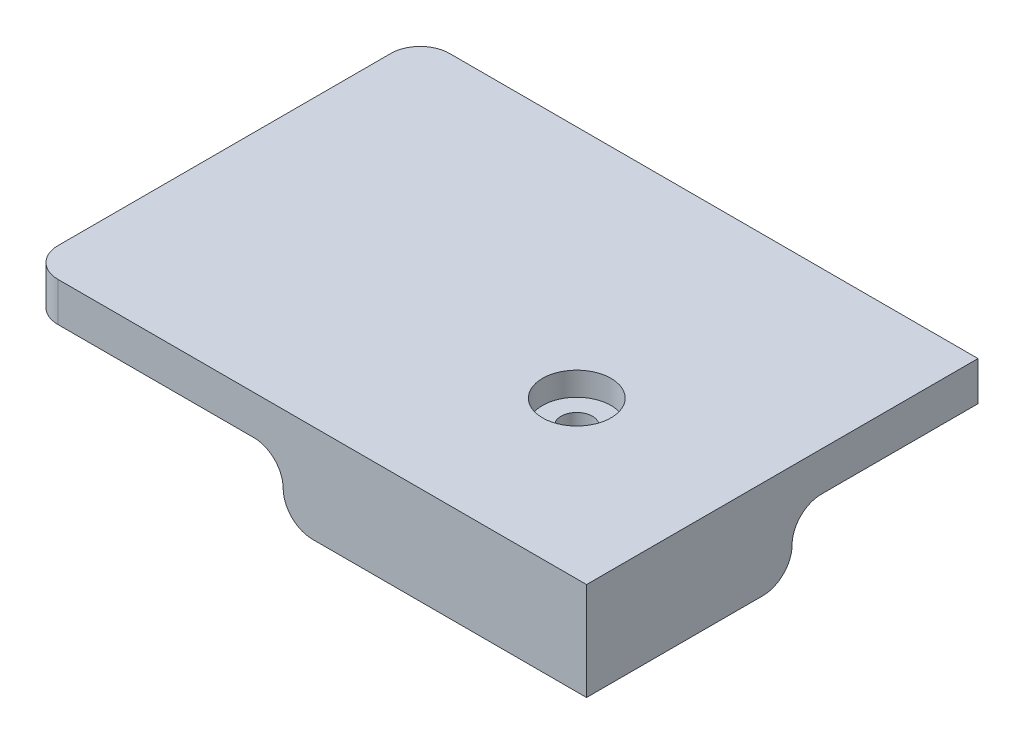
SolidWorks part; units mm, degrees
ref_plane "Front Plane" through (0, 0, 0) normal (0, 0, 1) x (1, 0, 0)
ref_plane "Top Plane" through (0, 0, 0) normal (0, 1, 0) x (1, 0, 0)
ref_plane "Right Plane" through (0, 0, 0) normal (1, 0, 0) x (0, 0, -1)
sketch "Sketch1" plane through (0, 0, 0) normal (0, 1, 0) x (1, 0, 0)
  line L5 (-28.5, 20) -> (28.5, 20)
  line L6 (-28.5, 20) -> (-28.5, -20)
  line L7 (-28.5, -20) -> (28.5, -20)
  line L8 (28.5, 20) -> (28.5, -20)
  line L9 (-28.5, 20) -> (28.5, -20) construction
  line L10 (-28.5, -20) -> (28.5, 20) construction
  point P0 (0, 0)
  dimension "D1" = 57
  dimension "D2" = 40
extrude "Boss-Extrude1" add sketch "Sketch1" against normal blind 4
sketch "Sketch2" plane through (0, -4, 0) normal (0, -1, 0) x (1, 0, 0)
  line L1 (28.5, 20) -> (-2.5, 20)
  line L2 (28.5, 20) -> (28.5, -1)
  line L3 (28.5, -1) -> (-2.5, -1)
  line L4 (-2.5, 20) -> (-2.5, -1)
  point P7 (0, 0)
  dimension "D1" = 21
  dimension "D2" = 31
extrude "Boss-Extrude2" add sketch "Sketch2" along normal blind 6
sketch "Sketch4" plane through (0, 0, 0) normal (0, 1, 0) x (1, 0, 0)
  line L0 (28.5, -20) -> (28.5, 20) construction
  line L1 (-28.5, -20) -> (28.5, -20) construction
  point P0 (11.5, -4)
  dimension "D1" = 17
  dimension "D2" = 16
hole_wizard "CBORE for M3 Pan Head Screw1" positions "Sketch5" profile "Sketch6" counterbore size "M3" standard "JIS" end condition up to next
sketch "Sketch5" plane through (0, 0, 0) normal (0, 1, 0) x (1, 0, 0)
  point P0 (11.5, -4)
sketch "Sketch6" plane through (11.5, 0, 4) normal (1, 0, 0) x (0, 0, 1)
  line L0 (0, 0) -> (0, 10)
  line L1 (0, 10) -> (1.6, 10)
  line L3 (1.6, 10) -> (1.6, 2.4)
  line L4 (1.6, 2.4) -> (3.5, 2.4)
  line L5 (3.5, 2.4) -> (3.5, 0)
  line L7 (3.5, 0) -> (0, 0)
  line L11 (0, -6.35) -> (0, 107.95) construction
  dimension "Thru Hole Dia." = 3.2
  dimension "Thru Hole Depth" = 10
  dimension "C'Bore Dia." = 7
  dimension "C'Bore Depth" = 2.4
fillet "Fillet1" radius 3 6 edges at (13, -10, -1) (-2.5, -10, 9.5) (13, -4, -1) (-2.5, -4, 9.5) (-28.5, -2, 20) (-28.5, -2, -20)
